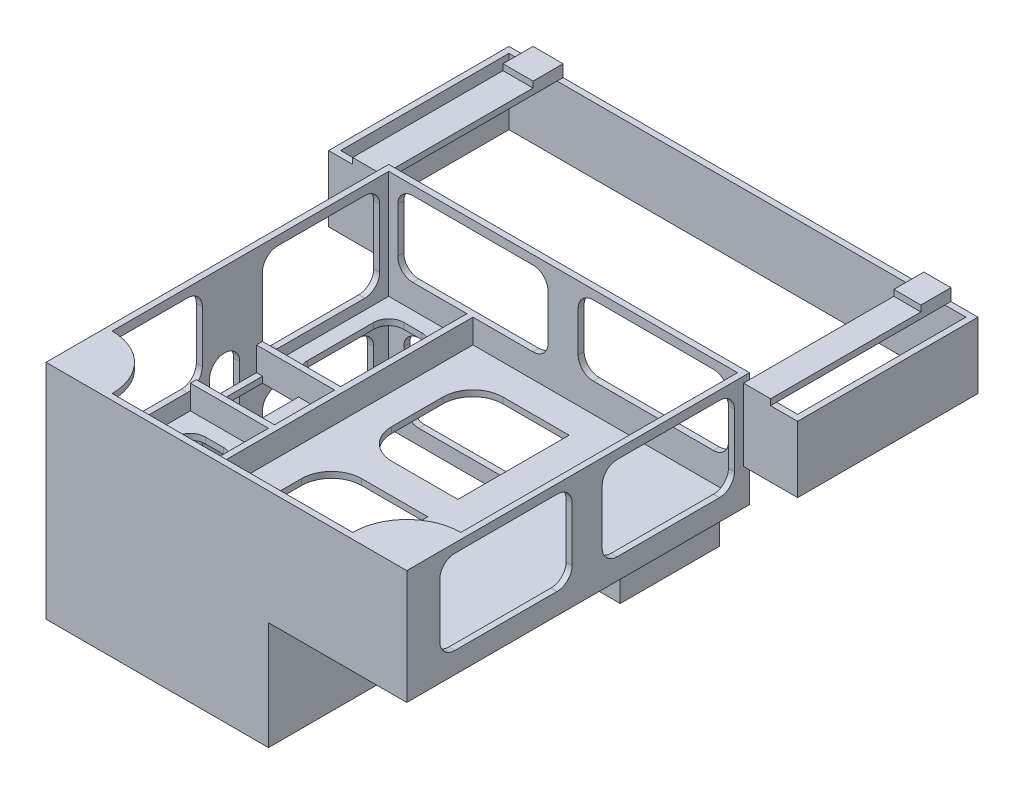
SolidWorks part; units mm, degrees
ref_plane "Front Plane" through (0, 0, 0) normal (0, 0, 1) x (1, 0, 0)
ref_plane "Top Plane" through (0, 0, 0) normal (0, 1, 0) x (1, 0, 0)
ref_plane "Right Plane" through (0, 0, 0) normal (1, 0, 0) x (0, 0, -1)
sketch "Sketch1" plane through (0, 0, 0) normal (0, 1, 0) x (1, 0, 0)
  line L1 (-113.8745, -60.9464) -> (-53.8745, -60.9464)
  line L2 (-113.8745, -60.9464) -> (-113.8745, -6.9464)
  line L3 (-113.8745, -6.9464) -> (-53.8745, -6.9464)
  line L4 (-53.8745, -60.9464) -> (-53.8745, -6.9464)
  dimension "D1" = 60
  dimension "D2" = 54
extrude "Boss-Extrude1" add sketch "Sketch1" along normal blind 38
sketch "Sketch2" plane through (0, 38, 0) normal (0, 1, 0) x (1, 0, 0)
  line L0 (-53.8745, -60.9464) -> (-53.8745, -6.9464) construction
  line L1 (-54.8745, -7.9464) -> (-98.8745, -7.9464)
  line L2 (-54.8745, -7.9464) -> (-54.8745, -59.9464)
  line L3 (-54.8745, -59.9464) -> (-98.8745, -59.9464)
  line L4 (-98.8745, -7.9464) -> (-98.8745, -59.9464)
  line L5 (-53.8745, -6.9464) -> (-113.8745, -6.9464) construction
  line L6 (-113.8745, -60.9464) -> (-53.8745, -60.9464) construction
  dimension "D1" = 1
  dimension "D2" = 1
  dimension "D3" = 1
  dimension "D4" = 44
extrude "Cut-Extrude1" cut sketch "Sketch2" against normal blind 19
sketch "Sketch3" plane through (0, 0, 0) normal (0, -1, 0) x (-1, 0, 0)
  line L0 (113.8745, -60.9464) -> (53.8745, -60.9464) construction
  line L1 (112.8745, -59.9464) -> (77.8745, -59.9464)
  line L2 (112.8745, -59.9464) -> (112.8745, -7.9464)
  line L3 (112.8745, -7.9464) -> (77.8745, -7.9464)
  line L4 (77.8745, -59.9464) -> (77.8745, -7.9464)
  line L5 (113.8745, -6.9464) -> (113.8745, -60.9464) construction
  line L6 (53.8745, -6.9464) -> (113.8745, -6.9464) construction
  dimension "D1" = 1
  dimension "D2" = 35
  dimension "D3" = 1
  dimension "D4" = 1
extrude "Cut-Extrude2" cut sketch "Sketch3" against normal blind 18
sketch "Sketch4" plane through (0, 18, 0) normal (0, -1, 0) x (-1, 0, 0)
  line L0 (77.8745, -59.9464) -> (112.8745, -59.9464) construction
  line L1 (111.8745, -39.9464) -> (105.8745, -39.9464)
  line L2 (111.8745, -39.9464) -> (111.8745, -29.9464)
  line L3 (111.8745, -29.9464) -> (105.8745, -29.9464)
  line L4 (105.8745, -39.9464) -> (105.8745, -29.9464)
  line L5 (112.8745, -7.9464) -> (77.8745, -7.9464) construction
  line L6 (112.8745, -59.9464) -> (112.8745, -7.9464) construction
  dimension "D1" = 20
  dimension "D2" = 22
  dimension "D3" = 1
  dimension "D4" = 6
extrude "Cut-Extrude3" cut sketch "Sketch4" against normal blind 38
sketch "Sketch5" plane through (0, 38, 0) normal (0, 1, 0) x (1, 0, 0)
  line L0 (-53.8745, -6.9464) -> (-113.8745, -6.9464) construction
  line L1 (-98.8745, -59.9464) -> (-112.8745, -59.9464)
  line L2 (-98.8745, -59.9464) -> (-98.8745, -7.9464)
  line L3 (-98.8745, -7.9464) -> (-112.8745, -7.9464)
  line L4 (-112.8745, -59.9464) -> (-112.8745, -7.9464)
  line L5 (-113.8745, -6.9464) -> (-113.8745, -60.9464) construction
  dimension "D1" = 1
  dimension "D2" = 1
extrude "Cut-Extrude5" cut sketch "Sketch5" against normal blind 15
sketch "Sketch6" plane through (0, 23, 0) normal (0, 1, 0) x (1, 0, 0)
  line L0 (-112.8745, -59.9464) -> (-98.8745, -59.9464) construction
  line L1 (-112.8745, -7.9464) -> (-99.8745, -7.9464)
  line L2 (-112.8745, -7.9464) -> (-112.8745, -59.9464)
  line L3 (-112.8745, -59.9464) -> (-99.8745, -59.9464)
  line L4 (-99.8745, -7.9464) -> (-99.8745, -59.9464)
  line L5 (-98.8745, -59.9464) -> (-98.8745, -7.9464) construction
  dimension "D1" = 1
extrude "Cut-Extrude6" cut sketch "Sketch6" against normal blind 4
sketch "Sketch8" plane through (0, 0, 0) normal (0, -1, 0) x (-1, 0, 0)
  line L0 (53.8745, -60.9464) -> (53.8745, -6.9464) construction
  line L1 (72.3745, -11.4464) -> (58.3745, -11.4464)
  line L2 (72.3745, -11.4464) -> (72.3745, -23.9464)
  line L3 (72.3745, -23.9464) -> (58.3745, -23.9464)
  line L4 (58.3745, -11.4464) -> (58.3745, -23.9464)
  line L6 (53.8745, -6.9464) -> (113.8745, -6.9464) construction
  dimension "D1" = 14
  dimension "D2" = 12.5
  dimension "D3" = 4.5
  dimension "D4" = 4.5
extrude "Cut-Extrude7" cut sketch "Sketch8" against normal blind 6
sketch "Sketch10" plane through (-72.3745, 0, 0) normal (1, 0, 0) x (0, 0, -1)
  line L0 (-11.4464, 6) -> (-11.4464, 0) construction
  line L1 (-23.9464, 6) -> (-11.4464, 6)
  line L2 (-23.9464, 6) -> (-23.9464, 1)
  line L3 (-23.9464, 1) -> (-11.4464, 1)
  line L4 (-11.4464, 6) -> (-11.4464, 1)
  line L5 (-23.9464, 0) -> (-11.4464, 0) construction
  dimension "D1" = 1
extrude "Cut-Extrude8" cut sketch "Sketch10" against normal blind 6
sketch "Sketch11" plane through (0, 0, 0) normal (0, -1, 0) x (1, 0, 0)
  line L0 (-113.8745, 60.9464) -> (-53.8745, 60.9464) construction
  line L1 (-68.3745, 50.9464) -> (-63.8745, 50.9464)
  line L2 (-68.3745, 50.9464) -> (-68.3745, 45.9464)
  line L3 (-68.3745, 45.9464) -> (-63.8745, 45.9464)
  line L4 (-63.8745, 50.9464) -> (-63.8745, 45.9464)
  line L5 (-53.8745, 60.9464) -> (-53.8745, 6.9464) construction
  dimension "D1" = 4.5
  dimension "D2" = 5
  dimension "D3" = 10
  dimension "D4" = 10
extrude "Cut-Extrude9" cut sketch "Sketch11" against normal blind 18
sketch "Sketch12" plane through (-68.3745, 0, 0) normal (1, 0, 0) x (0, 0, -1)
  line L0 (-50.9464, 18) -> (-50.9464, 0) construction
  line L1 (-45.9464, 18) -> (-50.9464, 18)
  line L2 (-45.9464, 18) -> (-45.9464, 1)
  line L3 (-45.9464, 1) -> (-50.9464, 1)
  line L4 (-50.9464, 18) -> (-50.9464, 1)
  line L5 (-50.9464, 0) -> (-45.9464, 0) construction
  dimension "D1" = 1
extrude "Cut-Extrude10" cut sketch "Sketch12" against normal blind 13
sketch "Sketch13" plane through (-113.8745, 0, 0) normal (-1, 0, 0) x (0, 0, 1)
  line L0 (35.233, 15) -> (35.233, 22) construction
  line L1 (32.733, 15) -> (32.733, 22)
  line L2 (37.733, 15) -> (37.733, 22)
  line L3 (59.9464, 18) -> (7.9464, 18) construction
  line L4 (39.9464, 19) -> (29.9464, 19) construction
  arc A0 (32.733, 15) -> (37.733, 15) centre (35.233, 15) ccw
  arc A1 (37.733, 22) -> (32.733, 22) centre (35.233, 22) ccw
  point P2 (35.233, 18.5)
  dimension "D1" = 3
  dimension "D2" = 3
  dimension "D3" = 2.5
extrude "Cut-Extrude11" cut sketch "Sketch13" against normal blind 1
sketch "Sketch14" plane through (0, 19, 0) normal (0, 1, 0) x (1, 0, 0)
  line L0 (-99.8745, -59.9464) -> (-99.8745, -7.9464) construction
  line L1 (-112.8745, -40.9464) -> (-99.8745, -40.9464)
  line L2 (-112.8745, -40.9464) -> (-112.8745, -39.9464)
  line L3 (-112.8745, -39.9464) -> (-99.8745, -39.9464)
  line L4 (-99.8745, -40.9464) -> (-99.8745, -39.9464)
  line L5 (-112.8745, -37.733) -> (-112.8745, -59.9464) construction
  line L6 (-105.8745, -39.9464) -> (-111.8745, -39.9464) construction
  dimension "D1" = 0
  dimension "D2" = 1
  dimension "D3" = 0
extrude "Boss-Extrude2" add sketch "Sketch14" along normal blind 4
sketch "Sketch15" plane through (0, 19, 0) normal (0, 1, 0) x (1, 0, 0)
  line L0 (-112.8745, -7.9464) -> (-112.8745, -32.733) construction
  line L1 (-112.8745, -29.9464) -> (-99.8745, -29.9464)
  line L2 (-112.8745, -29.9464) -> (-112.8745, -28.9464)
  line L3 (-112.8745, -28.9464) -> (-99.8745, -28.9464)
  line L4 (-99.8745, -29.9464) -> (-99.8745, -28.9464)
  line L5 (-99.8745, -39.9464) -> (-99.8745, -7.9464) construction
  line L6 (-111.8745, -29.9464) -> (-105.8745, -29.9464) construction
  dimension "D1" = 0
  dimension "D2" = 1
extrude "Boss-Extrude3" add sketch "Sketch15" along normal blind 4
sketch "Sketch16" plane through (0, 19, 0) normal (0, 1, 0) x (1, 0, 0)
  line L0 (-98.8745, -59.9464) -> (-54.8745, -59.9464) construction
  line L1 (-64.8745, -54.9464) -> (-88.8745, -54.9464)
  line L2 (-59.8745, -49.9464) -> (-59.8745, -41.4464)
  line L3 (-64.8745, -36.4464) -> (-88.8745, -36.4464)
  line L4 (-93.8745, -49.9464) -> (-93.8745, -41.4464)
  line L5 (-88.8745, -31.4464) -> (-64.8745, -31.4464)
  line L6 (-93.8745, -26.4464) -> (-93.8745, -17.9464)
  line L7 (-88.8745, -12.9464) -> (-64.8745, -12.9464)
  line L8 (-59.8745, -26.4464) -> (-59.8745, -17.9464)
  line L9 (-54.8745, -59.9464) -> (-54.8745, -7.9464) construction
  line L10 (-98.8745, -7.9464) -> (-98.8745, -59.9464) construction
  line L11 (-54.8745, -7.9464) -> (-98.8745, -7.9464) construction
  arc A0 (-64.8745, -31.4464) -> (-59.8745, -26.4464) centre (-64.8745, -26.4464) ccw
  arc A1 (-64.8745, -12.9464) -> (-59.8745, -17.9464) centre (-64.8745, -17.9464) cw
  arc A2 (-93.8745, -17.9464) -> (-88.8745, -12.9464) centre (-88.8745, -17.9464) cw
  arc A3 (-88.8745, -31.4464) -> (-93.8745, -26.4464) centre (-88.8745, -26.4464) cw
  arc A4 (-88.8745, -54.9464) -> (-93.8745, -49.9464) centre (-88.8745, -49.9464) cw
  arc A5 (-88.8745, -36.4464) -> (-93.8745, -41.4464) centre (-88.8745, -41.4464) ccw
  arc A6 (-59.8745, -41.4464) -> (-64.8745, -36.4464) centre (-64.8745, -41.4464) ccw
  arc A7 (-64.8745, -54.9464) -> (-59.8745, -49.9464) centre (-64.8745, -49.9464) ccw
  point P22 (-93.8745, -12.9464)
  point P25 (-93.8745, -31.4464)
  dimension "D9" = 5
  dimension "D1" = 5
  dimension "D2" = 5
  dimension "D3" = 5
  dimension "D4" = 5
  dimension "D5" = 5
  dimension "D6" = 5
  dimension "D7" = 5
  dimension "D8" = 18.5
extrude "Cut-Extrude12" cut sketch "Sketch16" against normal blind 1
sketch "Sketch17" plane through (0, 19, 0) normal (0, 1, 0) x (1, 0, 0)
  line L0 (-112.8745, -40.9464) -> (-112.8745, -59.9464) construction
  line L1 (-104.8745, -57.4464) -> (-107.8745, -57.4464)
  line L2 (-102.3745, -54.9464) -> (-102.3745, -45.9464)
  line L3 (-104.8745, -43.4464) -> (-107.8745, -43.4464)
  line L4 (-110.3745, -54.9464) -> (-110.3745, -45.9464)
  line L5 (-104.8745, -26.4464) -> (-107.8745, -26.4464)
  line L6 (-102.3745, -23.9464) -> (-102.3745, -12.9464)
  line L7 (-104.8745, -10.4464) -> (-107.8745, -10.4464)
  line L8 (-110.3745, -23.9464) -> (-110.3745, -12.9464)
  line L9 (-99.8745, -59.9464) -> (-99.8745, -40.9464) construction
  line L10 (-112.8745, -40.9464) -> (-99.8745, -40.9464) construction
  line L11 (-112.8745, -59.9464) -> (-99.8745, -59.9464) construction
  line L12 (-99.8745, -28.9464) -> (-112.8745, -28.9464) construction
  line L13 (-112.8745, -7.9464) -> (-112.8745, -28.9464) construction
  line L14 (-99.8745, -28.9464) -> (-99.8745, -7.9464) construction
  line L15 (-99.8745, -7.9464) -> (-112.8745, -7.9464) construction
  arc A0 (-102.3745, -12.9464) -> (-104.8745, -10.4464) centre (-104.8745, -12.9464) ccw
  arc A1 (-107.8745, -10.4464) -> (-110.3745, -12.9464) centre (-107.8745, -12.9464) ccw
  arc A2 (-107.8745, -26.4464) -> (-110.3745, -23.9464) centre (-107.8745, -23.9464) cw
  arc A3 (-104.8745, -26.4464) -> (-102.3745, -23.9464) centre (-104.8745, -23.9464) ccw
  arc A4 (-102.3745, -45.9464) -> (-104.8745, -43.4464) centre (-104.8745, -45.9464) ccw
  arc A5 (-107.8745, -43.4464) -> (-110.3745, -45.9464) centre (-107.8745, -45.9464) ccw
  arc A6 (-107.8745, -57.4464) -> (-110.3745, -54.9464) centre (-107.8745, -54.9464) cw
  arc A7 (-104.8745, -57.4464) -> (-102.3745, -54.9464) centre (-104.8745, -54.9464) ccw
  dimension "D9" = 2.5
  dimension "D1" = 2.5
  dimension "D2" = 2.5
  dimension "D3" = 2.5
  dimension "D4" = 2.5
  dimension "D5" = 2.5
  dimension "D6" = 2.5
  dimension "D7" = 2.5
  dimension "D8" = 2.5
extrude "Cut-Extrude13" cut sketch "Sketch17" against normal blind 1
sketch "Sketch18" plane through (-53.8745, 0, 0) normal (1, 0, 0) x (0, 0, -1)
  line L0 (-60.9464, 38) -> (-6.9464, 38) construction
  line L1 (-55.9464, 35.5) -> (-38.9464, 35.5)
  line L2 (-58.4464, 33) -> (-58.4464, 24)
  line L3 (-55.9464, 21.5) -> (-38.9464, 21.5)
  line L4 (-36.4464, 33) -> (-36.4464, 24)
  line L5 (-28.9464, 35.5) -> (-11.9464, 35.5)
  line L6 (-31.4464, 33) -> (-31.4464, 24)
  line L7 (-28.9464, 21.5) -> (-11.9464, 21.5)
  line L8 (-9.4464, 33) -> (-9.4464, 24)
  line L9 (-60.9464, 38) -> (-60.9464, 0) construction
  line L10 (-6.9464, 38) -> (-6.9464, 0) construction
  line L11 (-59.9464, 19) -> (-7.9464, 19) construction
  arc A0 (-31.4464, 24) -> (-28.9464, 21.5) centre (-28.9464, 24) ccw
  arc A1 (-11.9464, 21.5) -> (-9.4464, 24) centre (-11.9464, 24) ccw
  arc A2 (-11.9464, 35.5) -> (-9.4464, 33) centre (-11.9464, 33) cw
  arc A3 (-28.9464, 35.5) -> (-31.4464, 33) centre (-28.9464, 33) ccw
  arc A4 (-58.4464, 24) -> (-55.9464, 21.5) centre (-55.9464, 24) ccw
  arc A5 (-38.9464, 21.5) -> (-36.4464, 24) centre (-38.9464, 24) ccw
  arc A6 (-38.9464, 35.5) -> (-36.4464, 33) centre (-38.9464, 33) cw
  arc A7 (-55.9464, 35.5) -> (-58.4464, 33) centre (-55.9464, 33) ccw
  point P26 (-58.4464, 21.5)
  point P29 (-36.4464, 21.5)
  dimension "D9" = 2.5
  dimension "D1" = 2.5
  dimension "D2" = 2.5
  dimension "D3" = 2.5
  dimension "D4" = 2.5
  dimension "D5" = 5
  dimension "D6" = 22
  dimension "D7" = 2.5
  dimension "D8" = 2.5
extrude "Cut-Extrude14" cut sketch "Sketch18" against normal blind 1
sketch "Sketch19" plane through (0, 0, 6.9464) normal (0, 0, -1) x (-1, 0, 0)
  line L0 (53.8745, 38) -> (113.8745, 38) construction
  line L1 (58.8745, 35.5) -> (78.8745, 35.5)
  line L2 (56.3745, 33) -> (56.3745, 26.3041)
  line L3 (58.8745, 23.8041) -> (78.8745, 23.8041)
  line L4 (81.3745, 33) -> (81.3745, 26.3041)
  line L5 (88.8745, 35.5) -> (108.8745, 35.5)
  line L6 (86.3745, 33) -> (86.3745, 25.5)
  line L7 (88.8745, 23) -> (108.8745, 23)
  line L8 (111.3745, 33) -> (111.3745, 25.5)
  line L9 (113.8745, 38) -> (113.8745, 0) construction
  line L10 (53.8745, 38) -> (53.8745, 0) construction
  arc A0 (108.8745, 23) -> (111.3745, 25.5) centre (108.8745, 25.5) ccw
  arc A1 (108.8745, 35.5) -> (111.3745, 33) centre (108.8745, 33) cw
  arc A2 (88.8745, 35.5) -> (86.3745, 33) centre (88.8745, 33) ccw
  arc A3 (86.3745, 25.5) -> (88.8745, 23) centre (88.8745, 25.5) ccw
  arc A4 (78.8745, 23.8041) -> (81.3745, 26.3041) centre (78.8745, 26.3041) ccw
  arc A5 (78.8745, 35.5) -> (81.3745, 33) centre (78.8745, 33) cw
  arc A6 (56.3745, 26.3041) -> (58.8745, 23.8041) centre (58.8745, 26.3041) ccw
  arc A7 (58.8745, 35.5) -> (56.3745, 33) centre (58.8745, 33) ccw
  point P17 (111.3745, 23)
  point P24 (86.3745, 23)
  dimension "D8" = 2.5
  dimension "D1" = 2.5
  dimension "D2" = 2.5
  dimension "D3" = 2.5
  dimension "D4" = 2.5
  dimension "D5" = 5
  dimension "D6" = 25
  dimension "D7" = 0
extrude "Cut-Extrude15" cut sketch "Sketch19" against normal blind 60
sketch "Sketch20" plane through (-113.8745, 0, 0) normal (-1, 0, 0) x (0, 0, 1)
  line L0 (59.9464, 38) -> (7.9464, 38) construction
  line L1 (11.9464, 35.5) -> (26.4464, 35.5)
  line L2 (9.4464, 33) -> (9.4464, 23.222)
  line L3 (11.9464, 20.722) -> (26.4464, 20.722)
  line L4 (28.9464, 33) -> (28.9464, 23.222)
  line L5 (41.4464, 35.5) -> (55.9464, 35.5)
  line L6 (38.9464, 33) -> (38.9464, 24.3756)
  line L7 (41.4464, 21.8756) -> (55.9464, 21.8756)
  line L8 (58.4464, 33) -> (58.4464, 24.3756)
  line L9 (6.9464, 38) -> (6.9464, 0) construction
  line L10 (60.9464, 38) -> (60.9464, 0) construction
  line L11 (6.9464, 38) -> (60.9464, 38) construction
  arc A0 (38.9464, 24.3756) -> (41.4464, 21.8756) centre (41.4464, 24.3756) ccw
  arc A1 (55.9464, 21.8756) -> (58.4464, 24.3756) centre (55.9464, 24.3756) ccw
  arc A2 (55.9464, 35.5) -> (58.4464, 33) centre (55.9464, 33) cw
  arc A3 (41.4464, 35.5) -> (38.9464, 33) centre (41.4464, 33) ccw
  arc A4 (9.4464, 23.222) -> (11.9464, 20.722) centre (11.9464, 23.222) ccw
  arc A5 (26.4464, 20.722) -> (28.9464, 23.222) centre (26.4464, 23.222) ccw
  arc A6 (26.4464, 35.5) -> (28.9464, 33) centre (26.4464, 33) cw
  arc A7 (11.9464, 35.5) -> (9.4464, 33) centre (11.9464, 33) ccw
  point P18 (38.9464, 21.8756)
  point P21 (58.4464, 21.8756)
  dimension "D7" = 2.5
  dimension "D1" = 2.5
  dimension "D2" = 2.5
  dimension "D3" = 10
  dimension "D4" = 2.5
  dimension "D5" = 2.5
  dimension "D6" = 19.5
extrude "Cut-Extrude16" cut sketch "Sketch20" against normal blind 1
sketch "Sketch21" plane through (0, 0, 59.9464) normal (0, 0, -1) x (-1, 0, 0)
  line L0 (77.8745, 0) -> (112.8745, 0) construction
  line L1 (107.8745, 2.5) -> (82.8745, 2.5)
  line L2 (110.3745, 5) -> (110.3745, 13)
  line L3 (107.8745, 15.5) -> (82.8745, 15.5)
  line L4 (80.3745, 5) -> (80.3745, 13)
  line L5 (77.8745, 18) -> (77.8745, 0) construction
  line L6 (112.8745, 18) -> (112.8745, 0) construction
  line L7 (77.8745, 18) -> (112.8745, 18) construction
  arc A0 (110.3745, 13) -> (107.8745, 15.5) centre (107.8745, 13) ccw
  arc A1 (82.8745, 15.5) -> (80.3745, 13) centre (82.8745, 13) ccw
  arc A2 (82.8745, 2.5) -> (80.3745, 5) centre (82.8745, 5) cw
  arc A3 (107.8745, 2.5) -> (110.3745, 5) centre (107.8745, 5) ccw
  dimension "D5" = 2.5
  dimension "D1" = 2.5
  dimension "D2" = 2.5
  dimension "D3" = 2.5
  dimension "D4" = 2.5
extrude "Cut-Extrude17" cut sketch "Sketch21" along normal blind 100 and the other way blind 10
sketch "Sketch22" plane through (-112.8745, 0, 0) normal (1, 0, 0) x (0, 0, -1)
  line L0 (-59.9464, 0) -> (-7.9464, 0) construction
  line L1 (-12.9464, 2.5) -> (-26.4464, 2.5)
  line L2 (-10.4464, 5) -> (-10.4464, 13)
  line L3 (-12.9464, 15.5) -> (-26.4464, 15.5)
  line L4 (-28.9464, 5) -> (-28.9464, 13)
  line L5 (-41.4464, 2.5) -> (-54.9464, 2.5)
  line L6 (-38.9464, 5) -> (-38.9464, 13)
  line L7 (-41.4464, 15.5) -> (-54.9464, 15.5)
  line L8 (-57.4464, 5) -> (-57.4464, 13)
  line L9 (-7.9464, 18) -> (-7.9464, 0) construction
  line L10 (-32.733, 18) -> (-7.9464, 18) construction
  line L11 (-59.9464, 18) -> (-37.733, 18) construction
  line L12 (-59.9464, 18) -> (-59.9464, 0) construction
  arc A0 (-38.9464, 13) -> (-41.4464, 15.5) centre (-41.4464, 13) ccw
  arc A1 (-54.9464, 15.5) -> (-57.4464, 13) centre (-54.9464, 13) ccw
  arc A2 (-54.9464, 2.5) -> (-57.4464, 5) centre (-54.9464, 5) cw
  arc A3 (-41.4464, 2.5) -> (-38.9464, 5) centre (-41.4464, 5) ccw
  arc A4 (-26.4464, 2.5) -> (-28.9464, 5) centre (-26.4464, 5) cw
  arc A5 (-26.4464, 15.5) -> (-28.9464, 13) centre (-26.4464, 13) ccw
  arc A6 (-10.4464, 13) -> (-12.9464, 15.5) centre (-12.9464, 13) ccw
  arc A7 (-12.9464, 2.5) -> (-10.4464, 5) centre (-12.9464, 5) ccw
  point P30 (-28.9464, 15.5)
  point P33 (-10.4464, 15.5)
  dimension "D9" = 2.5
  dimension "D1" = 2.5
  dimension "D2" = 10
  dimension "D3" = 2.5
  dimension "D4" = 2.5
  dimension "D5" = 2.5
  dimension "D6" = 2.5
  dimension "D7" = 2.5
  dimension "D8" = 18.5
extrude "Cut-Extrude18" cut sketch "Sketch22" against normal blind 10
sketch "Sketch23" plane through (0, 38, 0) normal (0, 1, 0) x (1, 0, 0)
  line L1 (-112.8745, -59.9464) -> (-54.8745, -59.9464)
  line L2 (-112.8745, -59.9464) -> (-112.8745, -7.9464)
  line L3 (-112.8745, -7.9464) -> (-54.8745, -7.9464)
  line L4 (-54.8745, -59.9464) -> (-54.8745, -7.9464)
extrude "Boss-Extrude4" add sketch "Sketch23" against normal blind 1
sketch "Sketch24" plane through (0, 38, 0) normal (0, 1, 0) x (1, 0, 0)
  line L0 (-113.8745, -6.9464) -> (-113.8745, -60.9464) construction
  line L1 (-113.8745, -50.9464) -> (-53.8745, -50.9464)
  line L2 (-113.8745, -50.9464) -> (-113.8745, -16.9464)
  line L3 (-113.8745, -16.9464) -> (-53.8745, -16.9464)
  line L4 (-53.8745, -50.9464) -> (-53.8745, -16.9464)
  line L5 (-53.8745, -60.9464) -> (-53.8745, -6.9464) construction
  line L6 (-53.8745, -6.9464) -> (-113.8745, -6.9464) construction
  line L7 (-103.8745, -6.9464) -> (-63.8745, -6.9464)
  line L8 (-103.8745, -6.9464) -> (-103.8745, -60.9464)
  line L9 (-103.8745, -60.9464) -> (-63.8745, -60.9464)
  line L10 (-63.8745, -6.9464) -> (-63.8745, -60.9464)
  line L11 (-113.8745, -60.9464) -> (-53.8745, -60.9464) construction
  line L12 (-58.8745, -60.9464) -> (-56.3745, -60.9464) construction
  line M5 (-113.8745, -6.9464) -> (-113.8745, -60.9464)
  line M6 (-113.8745, -60.9464) -> (-53.8745, -60.9464)
  line M7 (-53.8745, -60.9464) -> (-53.8745, -6.9464)
  line M8 (-53.8745, -6.9464) -> (-113.8745, -6.9464)
  dimension "D1" = 10
  dimension "D2" = 10
  dimension "D3" = 10
  dimension "D4" = 10
extrude "Cut-Extrude20" cut sketch "Sketch24" against normal blind 1 contours L10 L1 L8 M6 | L3 L10 L1 M7 | L10 L8 L3 M8 | L10 L3 L8 L1 | L8 L3 L1 M5
fillet "Fillet1" radius 9 3 edges at (-103.8745, 37, 55.4464) (-108.3745, 37, 50.9464) (-103.8745, 37.5, 50.9464)
fillet "Fillet2" radius 9 3 edges at (-63.8745, 37, 12.4464) (-59.3745, 37, 16.9464) (-63.8745, 37.5, 16.9464)
fillet "Fillet3" radius 9 3 edges at (-63.8745, 37, 55.4464) (-63.8745, 37.5, 50.9464) (-59.3745, 37, 50.9464)
fillet "Fillet4" radius 9 3 edges at (-108.3745, 37, 16.9464) (-103.8745, 37, 12.4464) (-103.8745, 37.5, 16.9464)
sketch "Sketch27" plane through (0, 0, 6.9464) normal (0, 0, -1) x (-1, 0, 0)
  line L0 (53.8745, 38) -> (53.8745, 0) construction
  line L1 (53.8745, 24) -> (43.8745, 24)
  line L2 (53.8745, 24) -> (53.8745, 35)
  line L3 (53.8745, 35) -> (43.8745, 35)
  line L4 (43.8745, 24) -> (43.8745, 35)
  line L5 (113.8745, 38) -> (113.8745, 0) construction
  line L6 (113.8745, 24) -> (123.8745, 24)
  line L7 (113.8745, 24) -> (113.8745, 35)
  line L8 (113.8745, 35) -> (123.8745, 35)
  line L9 (123.8745, 24) -> (123.8745, 35)
  line L10 (63.8745, 37) -> (103.8745, 37) construction
  dimension "D1" = 2
  dimension "D2" = 2
  dimension "D3" = 80
  dimension "D4" = 10
  dimension "D5" = 11
  dimension "D6" = 11
extrude "Boss-Extrude10" add sketch "Sketch27" against normal blind 1
sketch "Sketch31" plane through (0, 0, 6.9464) normal (0, 0, -1) x (-1, 0, 0)
  line L0 (43.8745, 24) -> (53.8745, 24) construction
  line L1 (43.8745, 24) -> (44.8745, 24)
  line L2 (43.8745, 24) -> (43.8745, 35)
  line L3 (43.8745, 35) -> (44.8745, 35)
  line L4 (44.8745, 24) -> (44.8745, 35)
  line L5 (53.8745, 35) -> (43.8745, 35) construction
  line L6 (123.8745, 35) -> (113.8745, 35) construction
  line L7 (122.8745, 35) -> (123.8745, 35)
  line L8 (122.8745, 35) -> (122.8745, 24)
  line L9 (122.8745, 24) -> (123.8745, 24)
  line L10 (123.8745, 35) -> (123.8745, 24)
  dimension "D1" = 1
  dimension "D2" = 1
extrude "Boss-Extrude12" add sketch "Sketch31" along normal blind 29
sketch "Sketch33" plane through (-44.8745, 0, 0) normal (-1, 0, 0) x (0, 0, 1)
  line L0 (-22.0536, 24) -> (6.9464, 24) construction
  line L1 (-22.0536, 35) -> (-21.0536, 35)
  line L2 (-22.0536, 35) -> (-22.0536, 24)
  line L3 (-22.0536, 24) -> (-21.0536, 24)
  line L4 (-21.0536, 35) -> (-21.0536, 24)
  dimension "D1" = 1
extrude "Boss-Extrude13" add sketch "Sketch33" along normal blind 78
sketch "Sketch34" plane through (0, 35, 0) normal (0, 1, 0) x (1, 0, 0)
  line L0 (-123.8745, -7.9464) -> (-113.8745, -7.9464) construction
  line L1 (-123.8745, 22.0536) -> (-43.8745, 22.0536) construction
  line L2 (-118.8745, -7.9464) -> (-113.8745, -7.9464)
  line L3 (-118.8745, -7.9464) -> (-118.8745, 22.0536)
  line L4 (-118.8745, 22.0536) -> (-113.8745, 22.0536)
  line L5 (-113.8745, -7.9464) -> (-113.8745, 22.0536)
  line L7 (-53.8745, -7.9464) -> (-49.3745, -7.9464)
  line L8 (-53.8745, -7.9464) -> (-53.8745, 22.0536)
  line L9 (-53.8745, 22.0536) -> (-49.3745, 22.0536)
  line L10 (-49.3745, -7.9464) -> (-49.3745, 22.0536)
extrude "Boss-Extrude14" add sketch "Sketch34" along normal blind 1
sketch "Sketch35" plane through (-122.8745, 0, 0) normal (1, 0, 0) x (0, 0, -1)
  line L0 (21.0536, 24) -> (-6.9464, 24) construction
  line L1 (21.0536, 24) -> (-6.9464, 24)
  line L2 (21.0536, 24) -> (21.0536, 35)
  line L3 (21.0536, 35) -> (-6.9464, 35)
  line L4 (-6.9464, 24) -> (-6.9464, 35)
extrude "Boss-Extrude15" add sketch "Sketch35" along normal blind 1
sketch "Sketch37" plane through (-123.8745, 0, 0) normal (-1, 0, 0) x (0, 0, 1)
  line L1 (7.9464, 35) -> (-22.0536, 35)
  line L2 (7.9464, 35) -> (7.9464, 24)
  line L3 (7.9464, 24) -> (-22.0536, 24)
  line L4 (-22.0536, 35) -> (-22.0536, 24)
extrude "Cut-Extrude21" cut sketch "Sketch37" against normal blind 1
sketch "Sketch38" plane through (-44.8745, 0, 0) normal (-1, 0, 0) x (0, 0, 1)
  line L1 (6.9464, 35) -> (-21.0536, 35)
  line L2 (6.9464, 35) -> (6.9464, 24)
  line L3 (6.9464, 24) -> (-21.0536, 24)
  line L4 (-21.0536, 35) -> (-21.0536, 24)
extrude "Boss-Extrude16" add sketch "Sketch38" along normal blind 1
sketch "Sketch39" plane through (-43.8745, 0, 0) normal (1, 0, 0) x (0, 0, -1)
  line L1 (-7.9464, 24) -> (22.0536, 24)
  line L2 (-7.9464, 24) -> (-7.9464, 35)
  line L3 (-7.9464, 35) -> (22.0536, 35)
  line L4 (22.0536, 24) -> (22.0536, 35)
extrude "Cut-Extrude22" cut sketch "Sketch39" against normal blind 1
sketch "Sketch40" plane through (0, 0, 60.9464) normal (0, 0, 1) x (1, 0, 0)
  line L0 (-113.8745, 38) -> (-113.8745, 0) construction
  line L1 (-53.8745, 0) -> (-113.8745, 0)
  line L2 (-53.8745, 0) -> (-53.8745, 37)
  line L3 (-53.8745, 37) -> (-113.8745, 37)
  line L4 (-113.8745, 0) -> (-113.8745, 37)
  dimension "D1" = 37
extrude "Boss-Extrude17" add sketch "Sketch40" along normal blind 3
sketch "Sketch41" plane through (0, 0, 59.9464) normal (0, 0, -1) x (-1, 0, 0)
  line L1 (112.8745, 0) -> (77.8745, 0)
  line L2 (112.8745, 0) -> (112.8745, 18)
  line L3 (112.8745, 18) -> (77.8745, 18)
  line L4 (77.8745, 0) -> (77.8745, 18)
extrude "Cut-Extrude23" cut sketch "Sketch41" against normal blind 3
sketch "Sketch42" plane through (0, 0, 59.9464) normal (0, 0, -1) x (-1, 0, 0)
  line L0 (98.8745, 19) -> (54.8745, 19) construction
  line L1 (98.8745, 19) -> (54.8745, 19)
  line L2 (98.8745, 19) -> (98.8745, 37)
  line L3 (98.8745, 37) -> (54.8745, 37)
  line L4 (54.8745, 19) -> (54.8745, 37)
  line L5 (54.8745, 19) -> (54.8745, 37) construction
extrude "Cut-Extrude24" cut sketch "Sketch42" against normal blind 3
sketch "Sketch44" plane through (0, 0, 59.9464) normal (0, 0, -1) x (-1, 0, 0)
  line L0 (103.8745, 37) -> (98.8745, 37) construction
  line L1 (112.8745, 19) -> (99.8745, 19)
  line L2 (112.8745, 19) -> (112.8745, 37)
  line L3 (112.8745, 37) -> (99.8745, 37)
  line L4 (99.8745, 19) -> (99.8745, 37)
  dimension "D1" = 13
extrude "Cut-Extrude25" cut sketch "Sketch44" against normal blind 3
sketch "Sketch45" plane through (-98.8745, 0, 0) normal (1, 0, 0) x (0, 0, -1)
  line L0 (-62.9464, 37) -> (-59.9464, 37) construction
  line L1 (-62.9464, 37) -> (-59.9464, 37)
  line L2 (-62.9464, 37) -> (-62.9464, 23)
  line L3 (-62.9464, 23) -> (-59.9464, 23)
  line L4 (-59.9464, 37) -> (-59.9464, 23)
  line L5 (-60.9464, 23) -> (-7.9464, 23) construction
extrude "Cut-Extrude26" cut sketch "Sketch45" against normal blind 3
sketch "Sketch47" plane through (0, 38, 0) normal (0, 1, 0) x (1, 0, 0)
  line L1 (-113.8745, -6.9464) -> (-53.8745, -6.9464)
  line L2 (-113.8745, -6.9464) -> (-113.8745, -16.9464)
  line L3 (-113.8745, -16.9464) -> (-53.8745, -16.9464)
  line L4 (-53.8745, -6.9464) -> (-53.8745, -16.9464)
extrude "Cut-Extrude27" cut sketch "Sketch47" against normal blind 1
sketch "Sketch48" plane through (0, 38, 0) normal (0, 1, 0) x (1, 0, 0)
  line L1 (-113.8745, -60.9464) -> (-53.8745, -60.9464)
  line L2 (-113.8745, -60.9464) -> (-113.8745, -50.9464)
  line L3 (-113.8745, -50.9464) -> (-53.8745, -50.9464)
  line L4 (-53.8745, -60.9464) -> (-53.8745, -50.9464)
extrude "Cut-Extrude28" cut sketch "Sketch48" against normal blind 1
sketch "Sketch49" plane through (0, 37, 0) normal (0, 1, 0) x (1, 0, 0)
  line L0 (-53.8745, -63.9464) -> (-53.8745, -6.9464) construction
  line L1 (-113.8745, -63.9464) -> (-53.8745, -63.9464)
  line L2 (-113.8745, -63.9464) -> (-113.8745, -53.9464)
  line L3 (-113.8745, -53.9464) -> (-53.8745, -53.9464)
  line L4 (-53.8745, -63.9464) -> (-53.8745, -53.9464)
  dimension "D1" = 10
extrude "Boss-Extrude18" add sketch "Sketch49" against normal blind 1
sketch "Sketch50" plane through (0, 37, 0) normal (0, 1, 0) x (1, 0, 0)
  line L0 (-54.8745, -53.9464) -> (-112.8745, -53.9464) construction
  line L1 (-103.8745, -53.9464) -> (-63.8745, -53.9464)
  line L2 (-103.8745, -53.9464) -> (-103.8745, -62.9464)
  line L3 (-103.8745, -62.9464) -> (-63.8745, -62.9464)
  line L4 (-63.8745, -53.9464) -> (-63.8745, -62.9464)
  line L5 (-53.8745, -63.9464) -> (-113.8745, -63.9464) construction
  line L6 (-53.8745, -63.9464) -> (-53.8745, -6.9464) construction
  line L7 (-113.8745, -6.9464) -> (-113.8745, -63.9464) construction
  dimension "D1" = 1
  dimension "D2" = 10
  dimension "D3" = 10
extrude "Cut-Extrude29" cut sketch "Sketch50" against normal blind 1 contours L2 L1 L4 L3
fillet "Fillet5" radius 9 5 edges at (-108.3745, 36, 53.9464) (-108.3745, 37, 53.9464) (-103.8745, 36, 58.4464) (-103.8745, 36.5, 53.9464) (-103.8745, 37, 58.4464)
fillet "Fillet6" radius 9 5 edges at (-59.3745, 36, 53.9464) (-59.3745, 37, 53.9464) (-63.8745, 37, 58.4464) (-63.8745, 36.5, 53.9464) (-63.8745, 36, 58.4464)
sketch "Sketch51" plane through (0, 36, 0) normal (0, 1, 0) x (1, 0, 0)
  line L0 (-113.8745, 22.0536) -> (-118.8745, 22.0536) construction
  line L1 (-113.8745, 22.0536) -> (-118.8745, 22.0536)
  line L2 (-113.8745, 22.0536) -> (-113.8745, 17.0536)
  line L3 (-113.8745, 17.0536) -> (-118.8745, 17.0536)
  line L4 (-118.8745, 22.0536) -> (-118.8745, 17.0536)
  line L5 (-118.8745, 22.0536) -> (-118.8745, -7.9464) construction
  line L6 (-53.8745, 22.0536) -> (-53.8745, -6.9464) construction
  line L7 (-49.3745, 22.0536) -> (-53.8745, 22.0536)
  line L8 (-49.3745, 22.0536) -> (-49.3745, 17.0536)
  line L9 (-49.3745, 17.0536) -> (-53.8745, 17.0536)
  line L10 (-53.8745, 22.0536) -> (-53.8745, 17.0536)
  dimension "D1" = 5
extrude "Boss-Extrude19" add sketch "Sketch51" along normal blind 1
sketch "Sketch53" plane through (0, 0, 0) normal (0, -1, 0) x (-1, 0, 0)
  line L0 (53.8745, -63.9464) -> (53.8745, -6.9464) construction
  line L1 (53.8745, -34.3392) -> (76.8745, -34.3392)
  line L2 (53.8745, -34.3392) -> (53.8745, -43.9464)
  line L3 (53.8745, -43.9464) -> (76.8745, -43.9464)
  line L4 (76.8745, -34.3392) -> (76.8745, -43.9464)
  line L5 (113.8745, -63.9464) -> (53.8745, -63.9464) construction
  line L6 (53.8745, -52.9464) -> (76.8745, -52.9464)
  line L7 (53.8745, -52.9464) -> (53.8745, -63.9464)
  line L8 (53.8745, -63.9464) -> (76.8745, -63.9464)
  line L9 (76.8745, -52.9464) -> (76.8745, -63.9464)
  line L10 (77.8745, -7.9464) -> (77.8745, -62.9464) construction
  line L11 (53.8745, -43.9464) -> (61.8745, -43.9464)
  line L12 (53.8745, -43.9464) -> (53.8745, -52.9464)
  line L13 (53.8745, -52.9464) -> (61.8745, -52.9464)
  line L14 (61.8745, -43.9464) -> (61.8745, -52.9464)
  line L15 (68.3745, -45.9464) -> (63.8745, -45.9464) construction
  line L16 (63.8745, -45.9464) -> (63.8745, -50.9464) construction
  line L17 (63.8745, -50.9464) -> (68.3745, -50.9464) construction
  point P21 (63.8745, -48.4464)
  line M20 (53.8745, -6.9464) -> (53.8745, -63.9464)
  line M21 (53.8745, -63.9464) -> (113.8745, -63.9464)
  dimension "D1" = 1
  dimension "D2" = 1
  dimension "D3" = 2
  dimension "D4" = 2
  dimension "D5" = 2
extrude "Cut-Extrude30" cut sketch "Sketch53" against normal blind 18 contours L4 L1 L3 M20 | L14 L3 L6 M20 | L9 L6 M20 M21
sketch "Sketch54" plane through (0, 0, 0) normal (0, -1, 0) x (-1, 0, 0)
  line L0 (53.8745, -34.3392) -> (53.8745, -6.9464) construction
  line L1 (53.8745, -34.3392) -> (76.8745, -34.3392)
  line L2 (53.8745, -34.3392) -> (53.8745, -25.9464)
  line L3 (53.8745, -25.9464) -> (76.8745, -25.9464)
  line L4 (76.8745, -34.3392) -> (76.8745, -25.9464)
  line L5 (53.8745, -6.9464) -> (76.8745, -6.9464)
  line L6 (53.8745, -6.9464) -> (53.8745, -9.4464)
  line L7 (53.8745, -9.4464) -> (76.8745, -9.4464)
  line L8 (76.8745, -6.9464) -> (76.8745, -9.4464)
  line L9 (53.8745, -6.9464) -> (113.8745, -6.9464) construction
  line L10 (58.3745, -11.4464) -> (58.3745, -23.9464) construction
  line L11 (53.8745, -25.9464) -> (56.3745, -25.9464)
  line L12 (53.8745, -25.9464) -> (53.8745, -9.4464)
  line L13 (53.8745, -9.4464) -> (56.3745, -9.4464)
  line L14 (56.3745, -25.9464) -> (56.3745, -9.4464)
  line L15 (72.3745, -11.4464) -> (58.3745, -11.4464) construction
  line L16 (58.3745, -23.9464) -> (72.3745, -23.9464) construction
  line L17 (77.8745, -7.9464) -> (77.8745, -62.9464) construction
  line M22 (113.8745, -6.9464) -> (53.8745, -6.9464)
  line M23 (53.8745, -6.9464) -> (53.8745, -34.3392)
  line M24 (53.8745, -34.3392) -> (76.8745, -34.3392)
  dimension "D1" = 2
  dimension "D2" = 2
  dimension "D3" = 2
  dimension "D4" = 1
  dimension "D5" = 1
extrude "Cut-Extrude31" cut sketch "Sketch54" against normal blind 18 contours L4 L3 M24 M23 | L3 L14 L7 M23 | L8 L7 M22 M23
sketch "Sketch55" plane through (0, 19, 0) normal (0, 1, 0) x (1, 0, 0)
  line L0 (-77.8745, -12.9464) -> (-77.8745, -31.4464) construction
  line L1 (-77.8745, -57.7928) -> (-58.5121, -57.7928)
  line L2 (-77.8745, -57.7928) -> (-77.8745, -10.6433)
  line L3 (-77.8745, -10.6433) -> (-58.5121, -10.6433)
  line L4 (-58.5121, -57.7928) -> (-58.5121, -10.6433)
  dimension "D1" = 0
extrude "Boss-Extrude20" add sketch "Sketch55" against normal blind 1
sketch "Sketch57" plane through (0, 0, 0) normal (0, -1, 0) x (-1, 0, 0)
  line L1 (76.8745, -52.9464) -> (61.8745, -52.9464)
  line L2 (76.8745, -52.9464) -> (76.8745, -43.9464)
  line L3 (76.8745, -43.9464) -> (61.8745, -43.9464)
  line L4 (61.8745, -52.9464) -> (61.8745, -43.9464)
  point P4 (62.9872, -42.6074)
  point P5 (74.312, -48.3712)
  point P8 (83.9332, -49.8642)
extrude "Cut-Extrude32" cut sketch "Sketch57" against normal blind 15
sketch "Sketch58" plane through (-76.8745, 0, 0) normal (1, 0, 0) x (0, 0, -1)
  line L0 (-45.9464, 15) -> (-43.9464, 15) construction
  line L1 (-51.2363, 0.5985) -> (-44.9464, 0.5985)
  line L2 (-51.2363, 0.5985) -> (-51.2363, 15)
  line L3 (-51.2363, 15) -> (-44.9464, 15)
  line L4 (-44.9464, 0.5985) -> (-44.9464, 15)
  point P6 (-43.8493, 2.5399)
extrude "Boss-Extrude21" add sketch "Sketch58" against normal blind 1
sketch "Sketch59" plane through (0, 15, 0) normal (0, -1, 0) x (-1, 0, 0)
  line L1 (76.8745, -52.9464) -> (61.8745, -52.9464)
  line L2 (76.8745, -52.9464) -> (76.8745, -43.9464)
  line L3 (76.8745, -43.9464) -> (61.8745, -43.9464)
  line L4 (61.8745, -52.9464) -> (61.8745, -43.9464)
  point P4 (62.2491, -43.7306)
  point P5 (67.4306, -45.7722)
extrude "Boss-Extrude26" add sketch "Sketch59" along normal blind 1
sketch "Sketch60" plane through (0, 14, 0) normal (0, -1, 0) x (-1, 0, 0)
  line L0 (61.8745, -52.9464) -> (76.8745, -52.9464) construction
  line L1 (68.3745, -50.9464) -> (63.8745, -50.9464)
  line L2 (68.3745, -50.9464) -> (68.3745, -45.9464)
  line L3 (68.3745, -45.9464) -> (63.8745, -45.9464)
  line L4 (63.8745, -50.9464) -> (63.8745, -45.9464)
  line L5 (61.8745, -43.9464) -> (61.8745, -52.9464) construction
  line L6 (76.8745, -43.9464) -> (61.8745, -43.9464) construction
  point P4 (64.047, -46.4113)
  dimension "D1" = 2
  dimension "D2" = 2
  dimension "D3" = 4.5
  dimension "D4" = 2
extrude "Cut-Extrude33" cut sketch "Sketch60" against normal blind 1
sketch "Sketch61" plane through (0, 0, 0) normal (0, -1, 0) x (-1, 0, 0)
  line L1 (58.3745, -23.9464) -> (72.3745, -23.9464)
  line L2 (58.3745, -23.9464) -> (58.3745, -11.4464)
  line L3 (58.3745, -11.4464) -> (72.3745, -11.4464)
  line L4 (72.3745, -23.9464) -> (72.3745, -11.4464)
  point P4 (71.7541, -11.8205)
extrude "Cut-Extrude34" cut sketch "Sketch61" against normal blind 18
sketch "Sketch62" plane through (-77.8745, 0, 0) normal (-1, 0, 0) x (0, 0, 1)
  line L0 (23.9464, 6) -> (23.9464, 1) construction
  line L1 (23.9464, 18) -> (11.4464, 18)
  line L2 (23.9464, 18) -> (23.9464, 13)
  line L3 (23.9464, 13) -> (11.4464, 13)
  line L4 (11.4464, 18) -> (11.4464, 13)
  line L5 (11.4464, 1) -> (11.4464, 6) construction
  line L6 (7.9464, 18) -> (12.9464, 18) construction
  point P4 (16.2954, 12.9914)
  dimension "D1" = 0
  dimension "D2" = 0
  dimension "D3" = 0
  dimension "D4" = 5
extrude "Cut-Extrude35" cut sketch "Sketch62" against normal blind 18
sketch "Sketch63" plane through (0, 0, 0) normal (0, -1, 0) x (1, 0, 0)
  line L0 (-56.3745, 9.4464) -> (-76.8745, 9.4464) construction
  line L1 (-56.3745, 25.9464) -> (-76.8745, 25.9464)
  line L2 (-56.3745, 25.9464) -> (-56.3745, 9.4464)
  line L3 (-56.3745, 9.4464) -> (-76.8745, 9.4464)
  line L4 (-76.8745, 25.9464) -> (-76.8745, 9.4464)
  line L5 (-56.3745, 9.4464) -> (-76.8745, 9.4464) construction
extrude "Cut-Extrude36" cut sketch "Sketch63" against normal blind 12
sketch "Sketch64" plane through (-76.8745, 0, 0) normal (1, 0, 0) x (0, 0, -1)
  line L1 (-24.3075, 0.7139) -> (-10.7319, 0.7139)
  line L2 (-24.3075, 0.7139) -> (-24.3075, 7.4343)
  line L3 (-24.3075, 7.4343) -> (-10.7319, 7.4343)
  line L4 (-10.7319, 0.7139) -> (-10.7319, 7.4343)
extrude "Boss-Extrude27" add sketch "Sketch64" against normal blind 1
